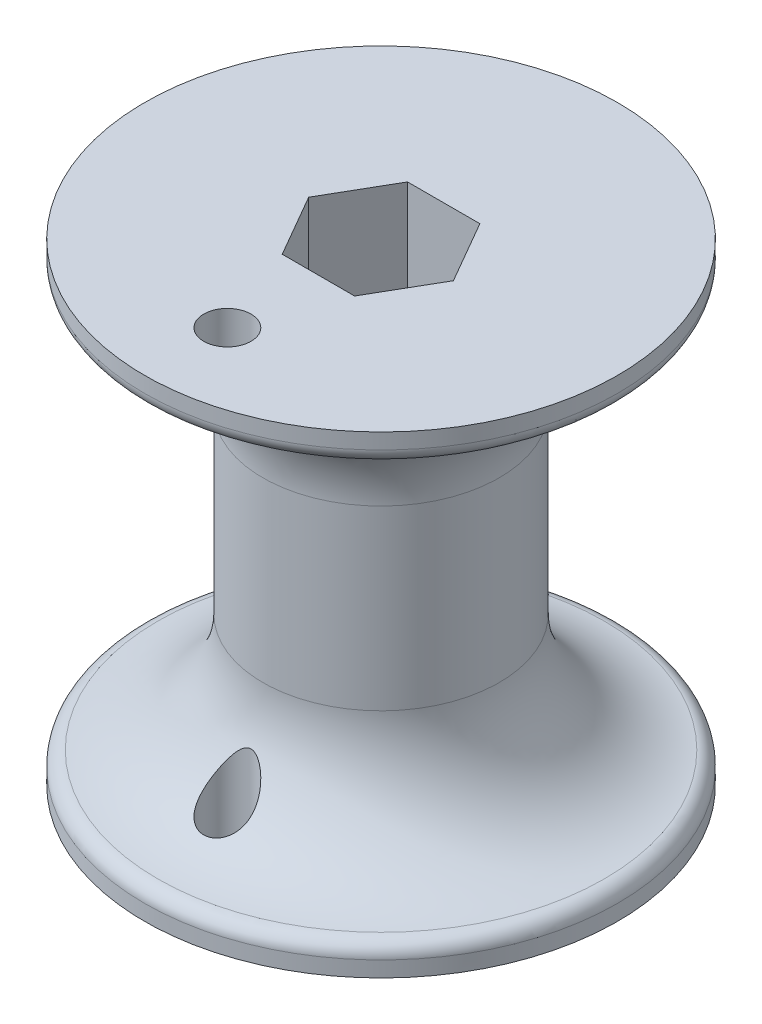
SolidWorks part; units mm, degrees
ref_plane "Front Plane" through (0, 0, 0) normal (0, 0, 1) x (1, 0, 0)
ref_plane "Top Plane" through (0, 0, 0) normal (0, 1, 0) x (1, 0, 0)
ref_plane "Right Plane" through (0, 0, 0) normal (1, 0, 0) x (0, 0, -1)
sketch "Sketch1" plane through (0, 0, 0) normal (1, 0, 0) x (0, 0, -1)
  line L0 (0, 0) -> (0, 25.4)
  line L1 (0, 25.4) -> (25.4, 25.4)
  line L2 (25.4, 25.4) -> (25.4, 22.225)
  line L4 (12.7, 9.525) -> (12.7, 0)
  line L5 (12.7, 0) -> (0, 0)
  arc A0 (12.7, 9.525) -> (25.4, 22.225) centre (25.4, 9.525) cw
  point P8 (0, 0)
  point P9 (0, 0)
  dimension "D1" = 25.4
  dimension "D3" = 3.175
  dimension "D4" = 12.7
  dimension "D5" = 25.4
  dimension "D6" = 9.525
revolve "Revolve1" add sketch "Sketch1" angle 360 about L0
mirror "Mirror1" about plane through (0, 0, -12.7) normal (0, -1, 0) of "Revolve1"
sketch "Sketch2" plane through (0, 25.4, 0) normal (0, 1, 0) x (1, 0, 0)
  line L7 (-3.8861, -6.731) -> (3.8861, -6.731)
  line L8 (3.8861, -6.731) -> (7.7723, 0)
  line L9 (7.7723, 0) -> (3.8861, 6.731)
  line L10 (3.8861, 6.731) -> (-3.8861, 6.731)
  line L11 (-3.8861, 6.731) -> (-7.7723, 0)
  line L12 (-7.7723, 0) -> (-3.8861, -6.731)
  circle A0 centre (0, 0) radius 6.731 construction
  circle A1 centre (0, -16.51) radius 2.54
  circle A2 centre (0, 0) radius 25.4 construction
  dimension "D2" = 5.08
  dimension "D1" = 13.462
  dimension "0." = 16.51
extrude "Cut-Extrude1" cut sketch "Sketch2" against normal through all
fillet "Fillet1" radius 1.5875 2 edges at (0, -22.225, -25.4) (0, 22.225, -25.4)
